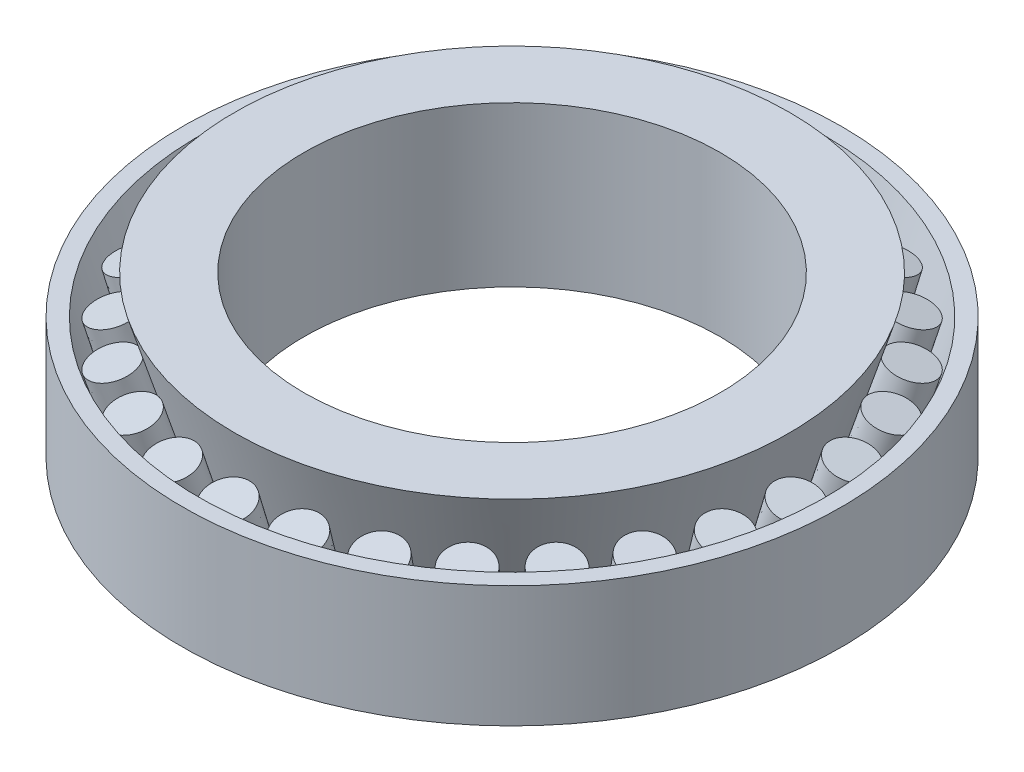
SolidWorks part; units mm, degrees
ref_plane "Plan de face" through (0, 0, 0) normal (0, 0, 1) x (1, 0, 0)
ref_plane "Plan de dessus" through (0, 0, 0) normal (0, 1, 0) x (1, 0, 0)
ref_plane "Plan de droite" through (0, 0, 0) normal (1, 0, 0) x (0, 0, -1)
sketch "Esquisse5" plane through (0, 0, 0) normal (0, 0, 1) x (1, 0, 0)
  line L0 (0, 0) -> (0, 38.3619) construction
  line L1 (-30, 0) -> (-33, 0)
  line L2 (-33, 0) -> (-40, 23)
  line L3 (-40, 23) -> (-30, 23)
  line L4 (-30, 23) -> (-30, 0)
  line L5 (-47.5, 17.5) -> (-47.5, 0)
  line L6 (-47.5, 0) -> (-40, 0)
  line L7 (-40, 0) -> (-45.1193, 17.5)
  line L8 (-45.1193, 17.5) -> (-47.5, 17.5)
  line L9 (-42.5596, 8.75) -> (0, 21.2) construction
  point P13 (-43.8506, 17.5)
  dimension "D1" = 60
  dimension "D2" = 95
  dimension "D3" = 23
  dimension "D4" = 17.5
  dimension "D5" = 66
  dimension "D6" = 80
  dimension "D7" = 23
  dimension "D8" = 1.8
  dimension "D9" = 80
revolve "Révolution1" add sketch "Esquisse5" angle 360 about L0
sketch "Esquisse6" plane through (0, 0, 0) normal (0, 0, 1) x (1, 0, 0)
  line L0 (-41.7227, 17.5) -> (-36.5, 0) construction
  line L1 (-40.9782, 15.0053) -> (-37.8509, 15.9386)
  line L2 (-40, 23) -> (-33, 0) construction
  line L3 (-37.8509, 15.9386) -> (-33.6675, 2.1932)
  line L4 (-33.6675, 2.1932) -> (-36.8694, 1.2376)
  line L5 (-40.9782, 15.0053) -> (-36.8694, 1.2376)
  line L6 (-45.1193, 17.5) -> (-38.3261, 17.5) construction
  line L7 (47.5, 17.5) -> (-47.5, 17.5) construction
  line L8 (-40, 0) -> (-33, 0) construction
  point P13 (-35.7816, 0)
revolve "Révolution2" add sketch "Esquisse6" angle 360 about L0
pattern_circular "Répétition circulaire1" count 28 over 360 about axis through (0, 23, 0) along (0, -1, 0) of "Révolution2"
